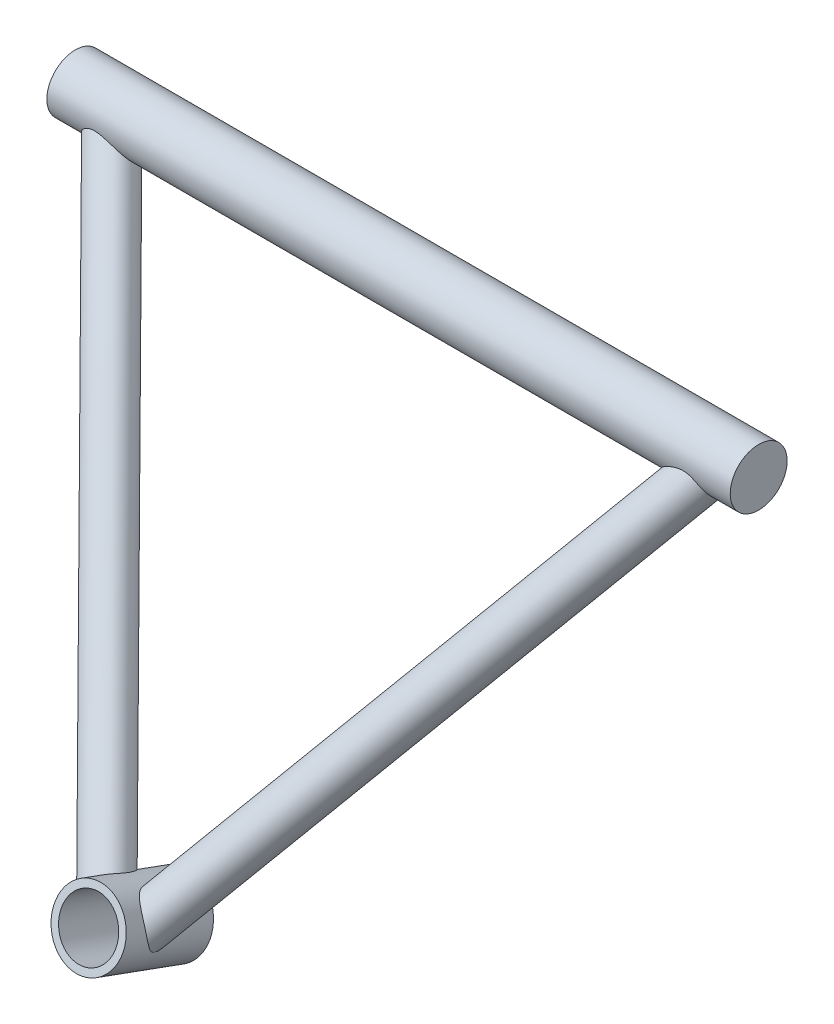
SolidWorks part; units mm, degrees
material "AISI 4130 Steel, normalized at 870C"
ref_plane "Front Plane" through (0, 0, 0) normal (0, 0, 1) x (1, 0, 0)
ref_plane "Top Plane" through (0, 0, 0) normal (0, 1, 0) x (1, 0, 0)
ref_plane "Right Plane" through (0, 0, 0) normal (1, 0, 0) x (0, 0, -1)
sketch "Sketch3" plane through (0, 0, 0) normal (0, 1, 0) x (1, 0, 0)
  line L0 (-5.08, -6.35) -> (5.08, -6.35) construction
  line L2 (0, -88.2205) -> (0, 88.2205) construction
  line L3 (5.08, 0) -> (-5.08, 0) construction
  dimension "D1" = 5.08
  dimension "D2" = 10.16
  dimension "D3" = 6.35
  dimension "D4" = 10.16
  dimension "D5" = 5.08
ref_plane "Plane1" through (0, 3.0196, 4.1561) normal (0, 0.5878, 0.809) x (1, 0, 0)
ref_plane "Plane3" through (0, 0, 0) normal (0, 0.342, 0.9397) x (-1, 0, 0)
sketch "Sketch1" plane through (0, 0, 0) normal (0, 0.342, 0.9397) x (1, 0, 0)
  circle A0 centre (0, 0) radius 15.875
  dimension "D1" = 31.75
extrude "Boss-Extrude1" add sketch "Sketch1" along normal mid plane 41.402 contours A0
sketch "Sketch4" plane through (0, 3.0196, 4.1561) normal (0, 0.5878, 0.809) x (1, 0, 0)
  line L0 (-5.08, -3.7324) -> (-132.08, 216.238)
  line L2 (0, -90.5202) -> (0, 90.5202) construction
  dimension "D2" = 30
  dimension "D3" = 254
sweep "Sweep1" add path "Sketch4" circular profile diameter 19.05 parameters "D3"=19.05
sketch "Sketch15" plane through (0, 3.0196, 4.1561) normal (0, 0.5878, 0.809) x (1, 0, 0)
  line L0 (5.08, -3.7324) -> (132.08, 216.238)
  line L1 (0, -90.5202) -> (0, 90.5202) construction
  dimension "D1" = 254
  dimension "D2" = 30
sweep "Sweep2" add path "Sketch15" circular profile diameter 19.05 parameters "D3"=19.05
sketch "Sketch36" plane through (-126.6538, 177.4747, -128.9429) normal (-0.5, 0.7006, -0.509) x (0.8656, 0.3849, -0.3204)
  circle A0 centre (-6.4316, -4.9279) radius 7.9375
  dimension "D1" = 15.875
extrude "Cut-Extrude2" cut sketch "Sketch36" against normal up to surface (272.4305 mm away) up to face at (14.6957, 3.6384, -7.5589)
sketch "Sketch37" plane through (126.6538, 177.4747, -128.9429) normal (0.5, 0.7006, -0.509) x (0.8656, -0.3849, 0.3204)
  circle A0 centre (6.4316, -4.9279) radius 7.9375
  dimension "D1" = 15.875
extrude "Cut-Extrude3" cut sketch "Sketch37" against normal up to surface (240.9848 mm away) up to face at (0.2372, -14.3112, 7.0906)
sketch "Sketch77" plane through (0, 7.0802, 19.4526) normal (0, 0.342, 0.9397) x (1, 0, 0)
  circle A1 centre (0, 0) radius 15.875
extrude "Boss-Extrude2" add sketch "Sketch77" against normal up to surface (41.402 mm away) up to face at (0, -21.9978, -14.023)
sketch "Sketch2" plane through (0, -7.0802, -19.4526) normal (0, -0.342, -0.9397) x (-1, 0, 0)
  circle A0 centre (0, 0) radius 12.7
  dimension "D1" = 25.4
extrude "Cut-Extrude1" cut sketch "Sketch2" against normal up to next
ref_plane "Plane2" through (0, 0, -127) normal (0, 0, 1) x (1, 0, 0)
ref_plane "Plane4" through (0, 177.8, 0) normal (0, 1, 0) x (1, 0, 0)
sketch "Sketch40" plane through (-106.934, 0, -127) normal (0, 0, 1) x (1, 0, 0)
  line L0 (108.4431, 184.15) -> (50108.4431, 184.15) construction
  line L1 (-45.466, 184.15) -> (259.334, 184.15)
  point P0 (106.934, 184.15)
  point P1 (106.934, 184.15)
  dimension "D1" = 304.8
  dimension "D5" = 184.15
sweep "Sweep5" add path "Sketch40" circular profile diameter 25.4 parameters "D3"=25.4
